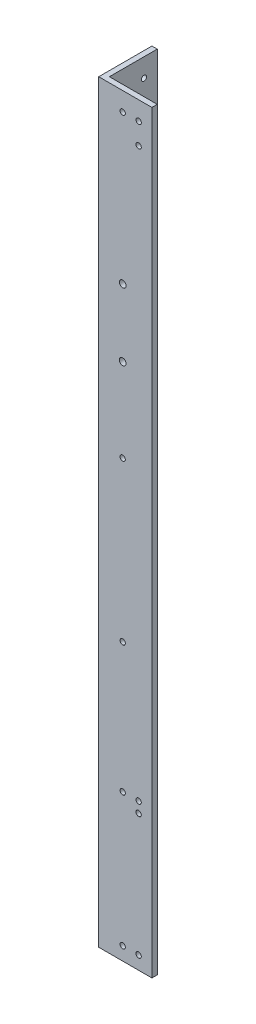
SolidWorks part; units mm, degrees
ref_plane "Front Plane" through (0, 0, 0) normal (0, 0, 1) x (1, 0, 0)
ref_plane "Top Plane" through (0, 0, 0) normal (0, 1, 0) x (1, 0, 0)
ref_plane "Right Plane" through (0, 0, 0) normal (1, 0, 0) x (0, 0, -1)
sketch "Sketch2" plane through (0, 0, 0) normal (0, 1, 0) x (1, 0, 0)
  line L0 (0, 31.75) -> (3.175, 31.75)
  line L1 (3.175, 31.75) -> (3.175, 3.175)
  line L2 (3.175, 3.175) -> (31.75, 3.175)
  line L3 (31.75, 3.175) -> (31.75, 0)
  line L4 (31.75, 0) -> (0, 0)
  line L5 (0, 0) -> (0, 31.75)
  point P9 (1.5875, 31.75)
  point P10 (31.75, 1.5875)
  dimension "D4" = 3.175
  dimension "D1" = 31.75
  dimension "D2" = 31.75
  dimension "D3" = 3.175
extrude "Boss-Extrude1" add sketch "Sketch2" along normal blind 450
sketch "FrontSideHoles-Sketch3" plane through (0, 0, 0) normal (0, 0, 1) x (1, 0, 0)
  line L0 (0, 0) -> (31.75, 0) construction
  line L1 (0, 450) -> (0, 0) construction
  circle A1 centre (23.8125, 81.1125) radius 1.5875
  circle A2 centre (14.2875, 87.4625) radius 1.5875
  circle A3 centre (23.8125, 87.4625) radius 1.5875
  circle A4 centre (14.2875, 438.8875) radius 1.5875
  circle A6 centre (23.8125, 438.8875) radius 1.5875
  circle A7 centre (23.8125, 426.1875) radius 1.5875
  circle A8 centre (14.2875, 350.0151) radius 2
  circle A9 centre (14.2875, 309.8151) radius 2
  circle A10 centre (14.2875, 260) radius 1.5875
  circle A11 centre (14.2875, 165) radius 1.5875
  circle A13 centre (14.2875, 7.9375) radius 1.5875
  circle A14 centre (23.8125, 7.9375) radius 1.5875
  dimension "D4" = 3.175
  dimension "D15" = 4
  dimension "D13" = 3.175
  dimension "D8" = 11.1125
  dimension "D11" = 40.2
  dimension "D9" = 309.8151
  dimension "D6" = 165
  dimension "D10" = 95
  dimension "D12" = 7.9375
  dimension "D3" = 9.525
  dimension "D2" = 14.2875
  dimension "D5" = 6.35
  dimension "D14" = 81.1125
  dimension "D7" = 12.7
  dimension "D16" = 14.2875
sketch "LeftSideHoles-Sketch4" plane through (0, 0, 0) normal (-1, 0, 0) x (0, 0, 1)
  line L0 (-31.75, 450) -> (0, 450) construction
  line L1 (0, 450) -> (0, 0) construction
  line L3 (-31.75, 0) -> (0, 0) construction
  circle A0 centre (-23.8125, 81.1125) radius 1.5875
  circle A1 centre (-14.2875, 81.1125) radius 1.5875
  circle A2 centre (-23.8125, 87.4625) radius 1.5875
  circle A4 centre (-23.8125, 438.8875) radius 1.5875
  circle A6 centre (-23.8125, 426.1875) radius 1.5875
  circle A7 centre (-14.2875, 426.1875) radius 1.5875
  circle A8 centre (-23.8125, 332.3776) radius 1.5875
  circle A9 centre (-14.2875, 332.3776) radius 1.5875
  circle A10 centre (-23.8125, 297.4526) radius 1.5875
  circle A11 centre (-14.2875, 297.4526) radius 1.5875
  circle A12 centre (-23.8125, 7.9375) radius 1.5875
  circle A13 centre (-14.2875, 7.9375) radius 1.5875
  circle A14 centre (-14.2875, 165) radius 1.5875
  circle A15 centre (-14.2875, 260) radius 1.5875
  circle A16 centre (-14.2875, 355) radius 1.5875
  dimension "D4" = 3.175
  dimension "D2" = 14.2875
  dimension "D5" = 6.35
  dimension "D7" = 12.7
  dimension "D3" = 81.1125
  dimension "D6" = 11.1125
  dimension "D10" = 7.9375
  dimension "D9" = 34.925
  dimension "D11" = 9.525
  dimension "D8" = 332.3776
  dimension "D12" = 165
  dimension "D13" = 95
  dimension "D14" = 95
extrude "FrontSideHoles-Cut-Extrude1" cut sketch "FrontSideHoles-Sketch3" against normal blind 3.175
extrude "LeftSideHoles-Cut-Extrude2" cut sketch "LeftSideHoles-Sketch4" against normal blind 3.175
equation "\"RailThickness\"= .125in'Spec"
equation "\"VSWidth\"= 1.25in'Spec"
equation "\"VSHeight\"= 1.25in'Spec"
equation "\"VSLength\"= 450mm"
equation "\"HoleOffsetFromEdge\"= \"RailThickness\" * 2.5"
equation "\"HoleOffsetFromSide\"= \"RailThickness\" * 3.5"
equation "\"LegHeight\"= 70mm'Space needed for PSU/Stepper/Electronics"
equation "\"VSBottomSideRailHoleY1FromBottomOfLowerRail\"= \"V1 BottomOfLowerRail\" + \"HoleOffsetFromSide\"'Equals 81.1125"
equation "\"VSSideRailHoleX1FromSide\"= \"HoleOffsetFromSide\" + \"RailThickness\""
equation "\"FasteningHoleDiameter\"= .125in"
equation "\"VSBottomSideRailHoleY2FromY1\"= \"LowerRailHeight\" - \"HoleOffsetFromSide\" - \"HoleOffsetFromEdge\"'Equals 6.35"
equation "\"VSTopSideRailHoleY1FromEdge\"= \"HoleOffsetFromEdge\" + \"RailThickness\""
equation "\"D4@FrontSideHoles-Sketch3\" = \"FasteningHoleDiameter\""
equation "\"D1@Boss-Extrude1\"=\"VSLength\""
equation "\"D4@LeftSideHoles-Sketch4\" = \"FasteningHoleDiameter\""
equation "\"D3@LeftSideHoles-Sketch4\"= \"VSBottomSideRailHoleY1FromBottomOfLowerRail\""
equation "\"D8@FrontSideHoles-Sketch3\" = \"VSTopSideRailHoleY1FromEdge\""
equation "\"D6@LeftSideHoles-Sketch4\" = \"VSTopSideRailHoleY1FromEdge\""
equation "\"VSMidSideRailHoleY1FromV8TopOfMidSideRail\"= \"V8 ToTopOfMidSideRail\" - \"HoleOffsetFromEdge\"'Equals 332.37764"
equation "\"LowerRailHeight\"= 1.00in"
equation "\"D1@Sketch2\"=\"VSHeight\""
equation "\"D2@Sketch2\"=\"VSWidth\""
equation "\"TopRailHeight\"= 1.25in"
equation "\"MidLeftOrRightSideRailHeight\"= 2.0in"
equation "\"D10@LeftSideHoles-Sketch4\"=\"HoleOffsetFromEdge\""
equation "\"VSMidSideRailHoleY2FromY1\"= \"MidLeftOrRightSideRailHeight\" - \"HoleOffsetFromEdge\" * 2'Equals 34.925"
equation "\"D9@LeftSideHoles-Sketch4\"=\"VSMidSideRailHoleY2FromY1\""
equation "\"VSSideRailHoleX2FromX1\"= \"VSWidth\" - \"VSSideRailHoleX1FromSide\" - \"HoleOffsetFromEdge\""
equation "\"D11@LeftSideHoles-Sketch4\"=\"VSSideRailHoleX2FromX1\""
equation "\"VSTopSideRailHoleY2FromY1\"= \"TopRailHeight\" - \"VSTopSideRailHoleY1FromEdge\" - \"HoleOffsetFromEdge\"'Equals 12.7"
equation "\"D7@LeftSideHoles-Sketch4\"=\"VSTopSideRailHoleY2FromY1\""
equation "\"BeltTensionerInnerHeight\"= \"20TGT2PulleyWidth\" * 2 + \"1mmSpacer\" * 3"
equation "\"20TGT2PulleyWidth\"= 8.7mm'The STL of the Pulley in the diagram is a bit larger"
equation "\"1mmSpacer\"= 1mm"
equation "\"BeltTensionerHeight\"= 60mm"
equation "\"D11@FrontSideHoles-Sketch3\"=\"VSBeltTensionerHoleY2FromY1\""
equation "\"VSBeltTensionerHoleY1FromBottomAlignedWithYAxisGantryBlockMiddle\"= \"V6 ToMiddleOfYAxisGantryBlock\" - \"MidLeftOrRightSideRailHeight\" / 2 + \"BeltTensionerMountingHoleOffsetFromTopOrBottom\""
equation "\"VSBeltTensionerHoleY2FromY1\"= \"BeltTensionerHeight\" - \"BeltTensionerMountingHoleOffsetFromTopOrBottom\" * 2"
equation "\"V1 BottomOfLowerRail\"= \"LegHeight\""
equation "\"StepperShaftLength\"= 24mm'Pulley will be attached to the end"
equation "\"ZAxisLeadScrewLength\"= 200mm"
equation "\"LM8UUHeight\"= 24mm'Spec"
equation "\"V2 ToBedAtTopOfZAxis\"= \"V1 BottomOfLowerRail\" - \"LowerEnclosureThickness\" + \"StepperShaftLength\" + \"ZAxisLeadScrewLength\" - \"LM8UUHeight\" / 2"
equation "\"HotEndToTopOfXAxisGB\"= 63.315144mm'Measured from the100.Should be 63.315144"
equation "\"TopOfGBToBottomOfLinearRail\"= \"LinearGBWidth\" / 2 + \"LinearRailWidth\" / 2"
equation "\"LinearGBWidth\"= 27mm'Spec"
equation "\"V5 ToBottomOfXAxisLinearRail\"= \"V4 ToTopOfBuildPlate/HotEndTip\" + \"HotEndToTopOfXAxisGB\" - \"TopOfGBToBottomOfLinearRail\""
equation "\"LinearRailWidth\"= 12mm'Spec"
equation "\"V6 ToMiddleOfYAxisGantryBlock\"= \"V5 ToBottomOfXAxisLinearRail\" - \"GABHeight\" / 2'Equals 325.31514"
equation "\"GABUpperHeight\"= 6mm"
equation "\"GABMidWallHeight\"= 28mm'Must equal 28 or changes alignment"
equation "\"D8@LeftSideHoles-Sketch4\"= \"VSMidSideRailHoleY1FromV8TopOfMidSideRail\""
equation "\"BedToBuildPlateStandoffLength\"= 15mm"
equation "\"BuildPlateHeight\"= 8mm'Spec"
equation "\"V4 ToTopOfBuildPlate/HotEndTip\"= \"V2 ToBedAtTopOfZAxis\" + \"BedToBuildPlateStandoffLength\" + \"BuildPlateHeight\""
equation "\"D9@FrontSideHoles-Sketch3\"=\"VSBeltTensionerHoleY1FromBottomAlignedWithYAxisGantryBlockMiddle\""
equation "\"V8 ToTopOfMidSideRail\"= \"V6 ToMiddleOfYAxisGantryBlock\" + \"MidSideRailVerticalOffset\""
equation "\"VSEnclosureOffsets\"= ( \"VSLength\" - \"LegHeight\" ) / 4"
equation "\"D6@FrontSideHoles-Sketch3\"=\"LegHeight\" + \"VSEnclosureOffsets\""
equation "\"D10@FrontSideHoles-Sketch3\"=\"VSEnclosureOffsets\""
equation "\"D12@FrontSideHoles-Sketch3\"=\"HoleOffsetFromEdge\""
equation "\"D13@LeftSideHoles-Sketch4\"=\"VSEnclosureOffsets\""
equation "\"D12@LeftSideHoles-Sketch4\"=\"LegHeight\" + \"VSEnclosureOffsets\""
equation "\"D3@FrontSideHoles-Sketch3\"=\"VSSideRailHoleX2FromX1\""
equation "\"D2@FrontSideHoles-Sketch3\"=\"VSSideRailHoleX1FromSide\""
equation "\"D5@FrontSideHoles-Sketch3\"=\"VSBottomSideRailHoleY2FromY1\""
equation "\"D14@FrontSideHoles-Sketch3\"=\"VSBottomSideRailHoleY1FromBottomOfLowerRail\""
equation "\"D7@FrontSideHoles-Sketch3\"=\"VSTopSideRailHoleY2FromY1\""
equation "\"D5@LeftSideHoles-Sketch4\"=\"VSBottomSideRailHoleY2FromY1\""
equation "\"BeltTensionerMountingHoleDiameter\"= 4.0mm"
equation "\"D15@FrontSideHoles-Sketch3\"=\"BeltTensionerMountingHoleDiameter\""
equation "\"LowerEnclosureThickness\"= 5mm"
equation "\"GABLowerHeight\"= 3mm"
equation "\"GABHeight\"= \"GABLowerHeight\" + \"GABMidWallHeight\" + \"GABUpperHeight\""
equation "\"D14@LeftSideHoles-Sketch4\"=\"VSEnclosureOffsets\""
equation "\"BeltTensionerMountingHoleOffsetFromTopOrBottom\"= ( \"BeltTensionerHeight\" - \"BeltTensionerInnerHeight\" ) / 4"
equation "\"D13@FrontSideHoles-Sketch3\"=\"FasteningHoleDiameter\""
equation "\"VSBeltTensionerXMountingHoleOffsetFromSide\"= \"BeltTensionerMountingHoleOffsetFromEdge\" + \"RailThickness\" * 2"
equation "\"BeltTensionerMountingHoleOffsetFromEdge\"= \"HoleOffsetFromEdge\""
equation "\"D16@FrontSideHoles-Sketch3\"=\"VSBeltTensionerXMountingHoleOffsetFromSide\""
equation "\"MidSideRailVerticalOffset\"= \"LinearRailWidth\" + 3mm'Allows space for RodStabilizer to attach to bottom of MidSideRail"
